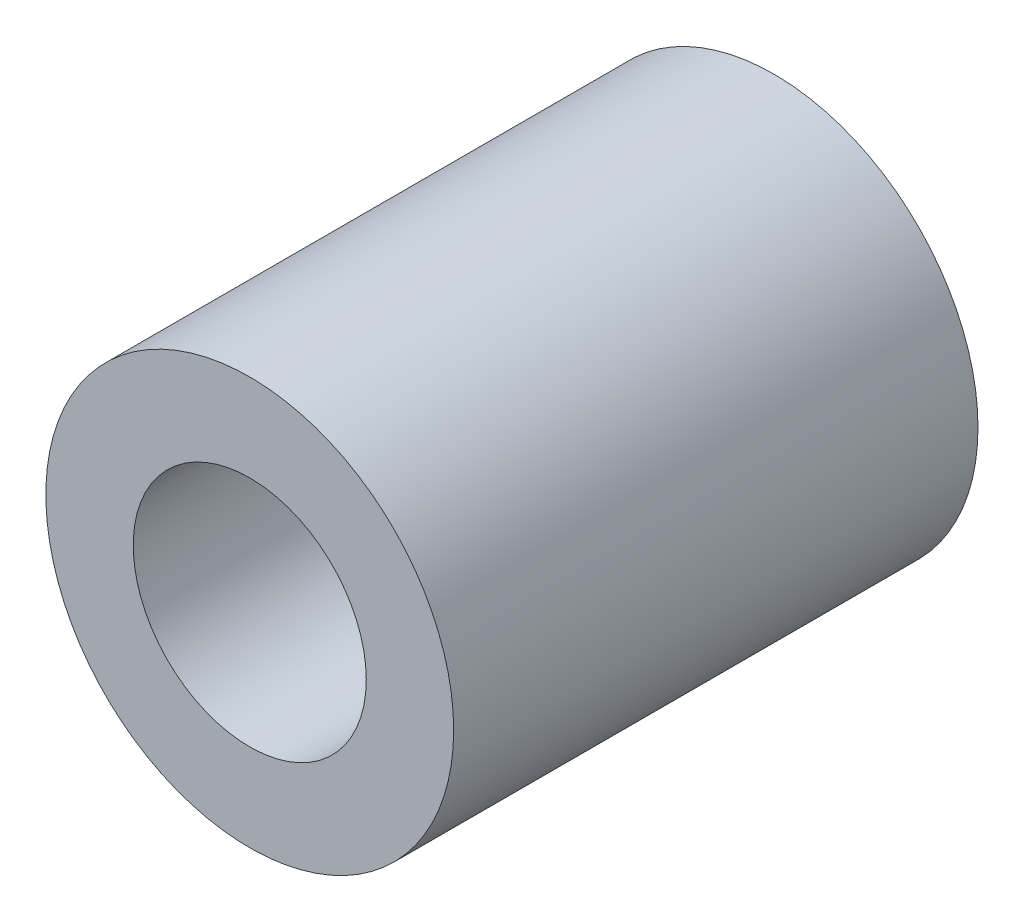
SolidWorks part; units mm, degrees
ref_plane "前视基准面" through (0, 0, 0) normal (0, 0, 1) x (1, 0, 0)
ref_plane "上视基准面" through (0, 0, 0) normal (0, 1, 0) x (1, 0, 0)
ref_plane "右视基准面" through (0, 0, 0) normal (1, 0, 0) x (0, 0, -1)
sketch "草图1" plane through (0, 0, 0) normal (0, 0, 1) x (1, 0, 0)
  circle A0 centre (0, 0) radius 3.5
extrude "凸台-拉伸1" add sketch "草图1" along normal blind 10
sketch "草图2" plane through (0, 0, 10) normal (0, 0, 1) x (1, 0, 0)
  circle A0 centre (0, 0) radius 2
extrude "切除-拉伸1" cut sketch "草图2" against normal blind 9
hole_wizard "大小mm 暗销孔2" positions "草图7" profile "草图8" hole size "Ø2.0" standard "GB" end condition through all
sketch "草图7" plane through (0, 0, 1) normal (0, 0, 1) x (1, 0, 0)
  point P0 (0, 0)
sketch "草图8" plane through (0, 0, 1) normal (1, 0, 0) x (0, -1, 0)
  line L0 (0, 0) -> (0, 1)
  line L1 (0, 1) -> (1, 1)
  line L2 (1, 1) -> (1, 0.025)
  line L3 (1, 0.025) -> (1.025, 0)
  line L5 (1.025, 0) -> (0, 0)
  line L6 (-1, 0.025) -> (-1.025, 0) construction
  line L11 (0, -6.35) -> (0, 107.95) construction
  dimension "通孔孔直径" = 2
  dimension "通孔孔深度" = 1
  dimension "近端锥形沉头孔直径" = 2.05
  dimension "近端锥形沉头孔角度" = 90
sketch "草图10" plane through (0, 0, 10) normal (0, 0, 1) x (1, 0, 0)
  circle A1 centre (0, 0) radius 3.5
  circle A2 centre (0, 0) radius 3.5
  dimension "D1" = 0
extrude "切除-拉伸2" cut sketch "草图10" against normal blind 1
